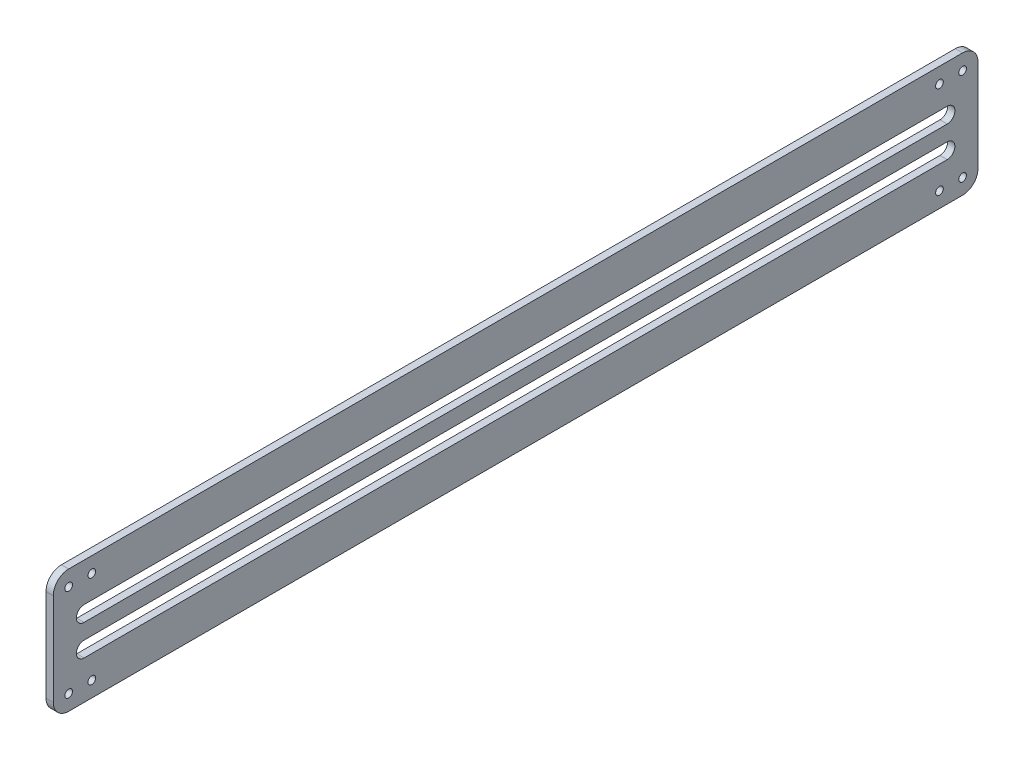
SolidWorks part; units mm, degrees
ref_plane "Front Plane" through (0, 0, 0) normal (0, 0, 1) x (1, 0, 0)
ref_plane "Top Plane" through (0, 0, 0) normal (0, 1, 0) x (1, 0, 0)
ref_plane "Right Plane" through (0, 0, 0) normal (1, 0, 0) x (0, 0, -1)
sketch "Sketch1" plane through (0, 0, 0) normal (1, 0, 0) x (0, 0, -1)
  line L1 (-184.15, -25.4) -> (184.15, -25.4)
  line L2 (-190.5, -19.05) -> (-190.5, 19.05)
  line L3 (-184.15, 25.4) -> (184.15, 25.4)
  line L4 (190.5, -19.05) -> (190.5, 19.05)
  line L5 (-190.5, -25.4) -> (190.5, 25.4) construction
  line L6 (-190.5, 25.4) -> (190.5, -25.4) construction
  arc A0 (184.15, 25.4) -> (190.5, 19.05) centre (184.15, 19.05) cw
  arc A1 (190.5, -19.05) -> (184.15, -25.4) centre (184.15, -19.05) cw
  arc A2 (-184.15, -25.4) -> (-190.5, -19.05) centre (-184.15, -19.05) cw
  arc A3 (-190.5, 19.05) -> (-184.15, 25.4) centre (-184.15, 19.05) cw
  point P0 (0, 0)
  dimension "D3" = 6.35
  dimension "D1" = 381
  dimension "D2" = 50.8
extrude "Outer Cut" add sketch "Sketch1" along normal mid plane 2.9972
sketch "Sketch2" plane through (1.4986, 0, 0) normal (1, 0, 0) x (0, 0, -1)
  line L0 (-190.5, 0) -> (190.5, 0) construction
  line L1 (-190.5, 19.05) -> (-190.5, -19.05) construction
  line L2 (190.5, -19.05) -> (190.5, 19.05) construction
  line L3 (-177.8, 6.35) -> (177.8, 6.35) construction
  line L4 (-177.8, 9.525) -> (177.8, 9.525)
  line L5 (-177.8, 3.175) -> (177.8, 3.175)
  line L6 (-177.8, -6.35) -> (177.8, -6.35) construction
  line L7 (-177.8, -9.525) -> (177.8, -9.525)
  line L8 (-177.8, -3.175) -> (177.8, -3.175)
  arc A0 (-177.8, 9.525) -> (-177.8, 3.175) centre (-177.8, 6.35) ccw
  arc A1 (177.8, 3.175) -> (177.8, 9.525) centre (177.8, 6.35) ccw
  arc A2 (-177.8, -9.525) -> (-177.8, -3.175) centre (-177.8, -6.35) cw
  arc A3 (177.8, -3.175) -> (177.8, -9.525) centre (177.8, -6.35) cw
  point P2 (0, 6.35)
  point P16 (0, -6.35)
  dimension "D1" = 6.35
  dimension "D2" = 12.7
  dimension "D3" = 12.7
  dimension "D4" = 12.7
extrude "Slots" cut sketch "Sketch2" against normal through all
sketch "Sketch3" plane through (1.4986, 0, 0) normal (1, 0, 0) x (0, 0, -1)
  line L0 (-190.5, 19.05) -> (-190.5, -19.05) construction
  line L1 (184.15, 25.4) -> (-184.15, 25.4) construction
  line L2 (0, 0) -> (0, 25.4) construction
  line L3 (0, 0) -> (-190.5, 0) construction
  circle A0 centre (-184.15, 19.05) radius 1.5875
  circle A1 centre (-174.625, 19.05) radius 1.5875
  circle A2 centre (-174.625, -19.05) radius 1.5875
  circle A3 centre (-184.15, -19.05) radius 1.5875
  circle A4 centre (174.625, 19.05) radius 1.5875
  circle A5 centre (184.15, 19.05) radius 1.5875
  circle A6 centre (184.15, -19.05) radius 1.5875
  circle A7 centre (174.625, -19.05) radius 1.5875
  dimension "D1" = 3.175
  dimension "D2" = 6.35
  dimension "D3" = 6.35
  dimension "D5" = 9.525
  dimension "D4" = 2
extrude "Mount Holes" cut sketch "Sketch3" against normal through all
